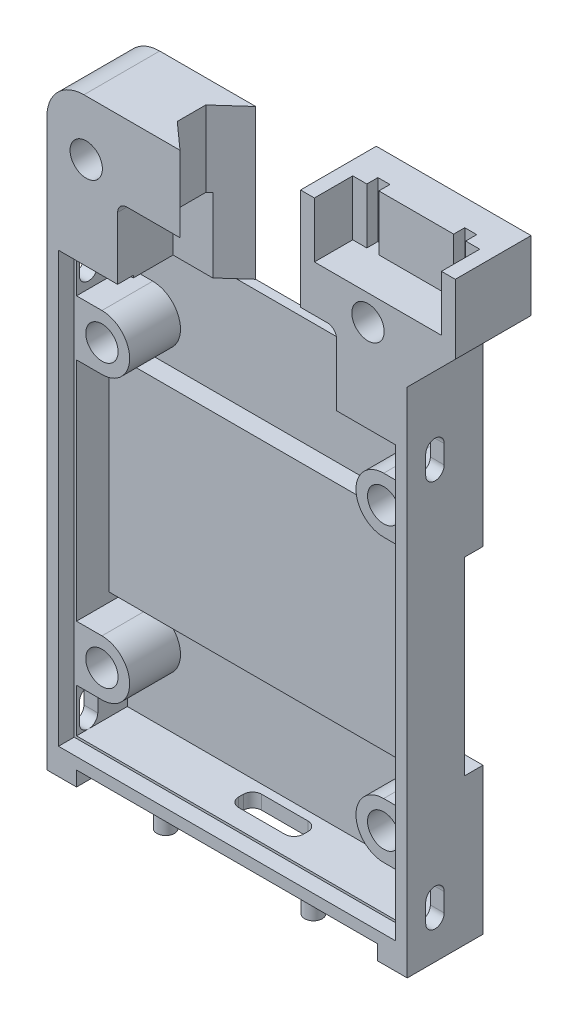
SolidWorks part; units mm, degrees
ref_plane "Front Plane" through (0, 0, 0) normal (0, 0, 1) x (1, 0, 0)
ref_plane "Top Plane" through (0, 0, 0) normal (0, 1, 0) x (1, 0, 0)
ref_plane "Right Plane" through (0, 0, 0) normal (1, 0, 0) x (0, 0, -1)
sketch "Sketch1" plane through (0, 0, 0) normal (0, 0, 1) x (1, 0, 0)
  line L0 (15.25, -20.35) -> (18, -20.35)
  line L1 (-19.5, -32.6) -> (19.5, -32.6)
  line L2 (-19.5, -32.6) -> (-19.5, 31.1)
  line L3 (-19.5, 31.1) -> (19.5, 31.1)
  line L4 (19.5, -32.6) -> (19.5, 31.1)
  line L5 (-15.25, -20.35) -> (-18, -20.35)
  line L6 (15.25, -26.35) -> (18, -26.35)
  line L7 (6.95, 31.1) -> (-15.5, 31.1) construction
  line L8 (-18, -31.1) -> (-18, 29.6)
  line L9 (-18, 29.6) -> (18, 29.6)
  line L10 (18, -31.1) -> (18, 29.6)
  line L11 (-18, -31.1) -> (18, -31.1)
  line L12 (-18, 14.9) -> (18, 14.9)
  line L13 (7.85, 14.9) -> (-4.95, 14.9) construction
  line L14 (-15.25, 4.15) -> (-18, 4.15)
  line L15 (-15.25, 10.15) -> (-18, 10.15)
  line L16 (15.25, 10.15) -> (18, 10.15)
  line L17 (15.25, 4.15) -> (18, 4.15)
  line L18 (-15.25, -26.35) -> (-18, -26.35)
  line L19 (19.5, -34.2) -> (19.5, -18.35) construction
  line L20 (-19.5, -34.2) -> (-19.5, -18.35) construction
  line L21 (15.3, -32.6) -> (-15.3, -32.6) construction
  line L22 (0, 31.1) -> (0, -32.6) construction
  line L23 (9.45, 26.9) -> (24.7, 26.9)
  line L24 (9.45, 26.9) -> (9.45, 33.9)
  line L25 (9.45, 33.9) -> (24.7, 33.9)
  line L26 (24.7, 26.9) -> (24.7, 33.9)
  line L27 (18, 29.6) -> (19.5, 31.1) construction
  line L28 (18.75, 30.35) -> (0, 30.35) construction
  line L29 (9.45, 26.9) -> (7.95, 26.9) construction
  line L30 (-7.95, 31.1) -> (7.95, 31.1)
  line L31 (-7.95, 31.1) -> (-7.95, 29.6)
  line L32 (-7.95, 29.6) -> (7.95, 29.6)
  line L33 (7.95, 31.1) -> (7.95, 29.6)
  line L34 (-7.95, 31.1) -> (7.95, 29.6) construction
  line L35 (-7.95, 29.6) -> (7.95, 31.1) construction
  line L36 (7.95, 26.9) -> (7.95, 29.6) construction
  line L37 (18, 29.6) -> (19.5, 29.6) construction
  line L38 (24.7, 26.4) -> (19.5, 21.2)
  line L39 (9.45, 33.9) -> (7.95, 33.9)
  line L40 (23.2, 33.9) -> (23.2, 26.9)
  line L41 (7.95, 33.9) -> (7.95, 31.1)
  line L42 (24.7, 30.4) -> (23.2, 30.4) construction
  line L43 (24.7, 26.9) -> (19.5, 26.9)
  line L44 (24.7, 26.9) -> (24.7, 26.4)
  line L45 (24.7, 26.4) -> (19.5, 26.4)
  line L46 (19.5, 26.9) -> (19.5, 26.4)
  circle A0 centre (15.25, -23.35) radius 1.75
  arc A1 (-15.5, 31.1) -> (-19.5, 27.1) centre (-15.5, 27.1) ccw construction
  circle A2 centre (15.25, -23.35) radius 3
  arc A3 (-15.5, 31.1) -> (-19.5, 27.1) centre (-15.5, 27.1) ccw
  arc A4 (-15.5, 29.6) -> (-18, 27.1) centre (-15.5, 27.1) ccw
  circle A6 centre (-15.25, -23.35) radius 1.75
  circle A7 centre (-15.25, -23.35) radius 1.75
  circle A8 centre (-15.25, 7.15) radius 1.75
  circle A9 centre (15.25, 7.15) radius 1.75
  circle A10 centre (15.25, 25.15) radius 1.75
  circle A11 centre (-15.25, 25.15) radius 1.75
  circle A12 centre (-15.25, -23.35) radius 3
  circle A13 centre (-15.25, -23.35) radius 3
  circle A14 centre (15.25, 7.15) radius 3
  circle A15 centre (-15.25, 7.15) radius 3
  dimension "D2" = 1.5
  dimension "D4" = 6
  dimension "D3" = 3.5
  dimension "D5" = 13.75
  dimension "D6" = 15.9
  dimension "D7" = 7
  dimension "D8" = 45
  dimension "D9" = 0.5
  dimension "D1" = 1.5
extrude "Base shape" add sketch "Sketch1" along normal up to surface (8.2 mm away) contours A15 L8 L9 L31 L3 A3 L2 L1 L4 L23 L10 A14 A2 L11 A12 | A12 L8 L18 | A12 L8 A6 | L8 A12 | A12 L5 L8 | A15 L8 L14 | A15 L8 A8 | L8 A15 | A15 L15 L8 | L23 A10 L24 L9 A4 L8 L12 L10 A11 | A4 L9 L8 | L33 L3 L31 L9 | L3 L33 L9 L24 | L24 L9 L10 L23 L4 L3 | L24 L23 L10 L9 | A14 L10 L16 | L10 A14 A9 | A14 L17 L10 | L10 A14 | L10 A2 L6 | A2 L10 A0 | L0 A2 L10 | A2 L10 | L40 L25 L24 L3 L4 L23 | L25 L40 L23 L26 | L38 L45 L4 | L45 L44 L23 L4 | L39 L41 L3 L24 region at (16.8481, -20.9099, 0) region at (17.3601, -20.8437, 0) region at (18.7469, -8.1, 0) region at (17.3601, -25.8563, 0) region at (18.1004, -23.35, 0) region at (17.3601, 4.6437, 0) region at (16.8481, 4.7099, 0) region at (18.1004, 7.15, 0) region at (17.3601, 9.6563, 0) region at (-17.3601, -25.8563, 0) region at (-0.6044, 21.831, 0) region at (-18.1004, -23.35, 0) region at (-17.9169, -23.35, 0) region at (13.725, 28.25, 0) region at (15.3803, 29.9053, 0) region at (-17.3601, -20.8437, 0) region at (22.1, 26.65, 0) region at (17.77, 31.4935, 0) region at (-17.3601, 9.6563, 0) region at (-17.4416, 29.0416, 0) region at (8.7, 30.35, 0) region at (21.2333, 24.6667, 0) region at (23.95, 30.4, 0) region at (-16.8481, 9.5901, 0) region at (-18.1004, 7.15, 0) region at (-17.3601, 4.6437, 0) region at (0, 30.35, 0) region at (8.7, 32.5, 0)
sketch "Sketch3" plane through (19.5, 0, 0) normal (1, 0, 0) x (0, 0, -1)
  line L1 (0, -18.35) -> (-2, -18.35)
  line L2 (0, -18.35) -> (0, 2.15)
  line L3 (0, 2.15) -> (-2, 2.15)
  line L4 (-2, -18.35) -> (-2, 2.15)
  line L5 (0, -18.35) -> (2, -18.35) construction
  line L6 (0, 2.15) -> (2, 2.15) construction
  line L7 (0, -32.6) -> (0, 21.2) construction
  dimension "D1" = 2
extrude "Strap cut" cut sketch "Sketch3" against normal through all
sketch "Sketch4" plane through (0, 31.1, 0) normal (0, 1, 0) x (1, 0, 0)
  line L2 (7.95, 0) -> (-5.0998, 0)
  line L4 (-15.5, 0) -> (7.95, 0) construction
  line L5 (-15.5, -8.2) -> (7.95, -8.2) construction
  line L6 (7.95, -8.2) -> (-5.0998, -8.2)
  line L12 (7.95, -8.3) -> (7.95, 0.1)
  line L13 (7.95, 0.1) -> (-4.9883, 0.1)
  line L14 (-4.9883, 0.1) -> (-7.95, -2.5553)
  line L15 (-7.95, -2.5553) -> (-7.95, -5.6447)
  line L16 (-7.95, -5.6447) -> (-4.9883, -8.3)
  line L17 (-4.9883, -8.3) -> (7.95, -8.3)
  line L18 (7.95, -8.3) -> (7.95, 0.1)
  line L19 (7.95, 0.1) -> (-4.9883, 0.1)
  line L20 (-4.9883, 0.1) -> (-7.95, -2.5553)
  line L21 (-7.95, -2.5553) -> (-7.95, -5.6447)
  line L22 (-7.95, -5.6447) -> (-4.9883, -8.3)
  line L23 (-4.9883, -8.3) -> (7.95, -8.3)
  dimension "D1" = 0.1
extrude "XT60 cut" cut sketch "Sketch4" against normal up to next contours L21 L22 L18 L20 region at (0.4142, 31.1, 4.1)
sketch "Sketch5" plane through (19.5, 0, 0) normal (1, 0, 0) x (0, 0, -1)
  line L1 (-8.2, -32.6) -> (-8.2, 21.2) construction
  line L2 (-6.2, -31.1) -> (-4.2, -31.1)
  line L3 (-6.2, -31.1) -> (-6.2, -27.1)
  line L4 (-6.2, -27.1) -> (-4.2, -27.1)
  line L5 (-4.2, -31.1) -> (-4.2, -27.1)
  line L6 (-8.2, -31.1) -> (0, -31.1) construction
  line L7 (-8.2, 14.9) -> (0, 14.9) construction
  line L8 (-6.2, 14.9) -> (-4.2, 14.9)
  line L9 (-6.2, 14.9) -> (-6.2, 10.9)
  line L10 (-6.2, 10.9) -> (-4.2, 10.9)
  line L11 (-4.2, 14.9) -> (-4.2, 10.9)
  line L14 (-5.2, -27.1) -> (-5.2, -31.1) construction
  line L15 (-5.2, 14.9) -> (-5.2, 10.9) construction
  circle A0 centre (-5.2, -28.1) radius 1
  circle A1 centre (-5.2, -30.1) radius 1
  circle A2 centre (-5.2, 13.9) radius 1
  circle A3 centre (-5.2, 11.9) radius 1
  point P20 (-5.2, -29.1)
  point P31 (-5.2, 12.9)
  dimension "D3" = 4
  dimension "D1" = 2
  dimension "D2" = 2
extrude "Power wires cut" cut sketch "Sketch5" against normal through all contours A2 | A3 | A3 A2 L9 | A3 L11 A2 | A1 | A0 | A1 L5 A0 | A1 A0 L3 region at (19.5, -30.1, 5.2) region at (19.5, -29.1, 5.9766) region at (19.5, -29.1, 4.4234) region at (19.5, -28.1, 5.2) region at (19.5, 13.9, 5.2) region at (19.5, 12.9, 5.9766) region at (19.5, 12.9, 4.4234) region at (19.5, 11.9, 5.2)
sketch "Sketch6" plane through (0, 0, 8.2) normal (0, 0, 1) x (1, 0, 0)
  line L5 (-10.85, 22.9) -> (10.85, 22.9)
  line L6 (11.85, 21.9) -> (11.85, 14.9)
  line L7 (11.85, 14.9) -> (-11.85, 14.9)
  line L12 (-11.85, 14.9) -> (-11.85, 21.9)
  line L13 (-10.85, 14.9) -> (-8.85, 14.9) construction
  arc A5 (-10.85, 22.9) -> (-11.85, 21.9) centre (-10.85, 21.9) ccw construction
  arc A6 (11.85, 21.9) -> (10.85, 22.9) centre (10.85, 21.9) ccw construction
  arc A7 (-10.85, 22.9) -> (-11.85, 21.9) centre (-10.85, 21.9) ccw
  arc A12 (11.85, 21.9) -> (10.85, 22.9) centre (10.85, 21.9) ccw
extrude "IO wires cut" cut sketch "Sketch6" against normal blind 6
sketch "Sketch7" plane through (-18, 0, 0) normal (1, 0, 0) x (0, 0, -1)
  line L6 (0, -18.35) -> (0, -20.35)
  line L7 (-2, -18.35) -> (0, -18.35)
  line L8 (-2, 2.15) -> (-2, -18.35)
  line L9 (0, 2.15) -> (-2, 2.15)
  line L12 (0, 3.15) -> (-3, 3.15)
  line L13 (-3, 3.15) -> (-3, -19.35)
  line L14 (-3, -19.35) -> (-1, -19.35)
  line L15 (-1, -19.35) -> (-1, -20.35)
  line L16 (-1, -20.35) -> (0, -20.35)
  line L17 (0, 3.15) -> (-1, 3.15)
  line L19 (0, -31.1) -> (-1, -31.1)
  line L22 (0, -31.1) -> (0, -20.35)
  line L23 (0, -20.35) -> (-1, -20.35)
  line L24 (-1, -31.1) -> (-1, -20.35)
  line L25 (0, 3.15) -> (0, 14.9)
  line L26 (0, 14.9) -> (-1, 14.9)
  line L27 (-1, 3.15) -> (-1, 14.9)
  line L28 (-5.2, 14.9) -> (0, 14.9) construction
  line L31 (0, -20.35) -> (0, -18.35) construction
  line L32 (0, 2.15) -> (-2, 2.15) construction
  line M48 (0, -20.35) -> (0, -18.35)
  line M49 (0, -18.35) -> (-2, -18.35)
  line M50 (-2, -18.35) -> (-2, 2.15)
  line M51 (-2, 2.15) -> (0, 2.15)
  line M52 (0, 2.15) -> (0, 4.15)
  line M53 (0, 4.15) -> (-8.2, 4.15)
  line M55 (-8.2, -20.35) -> (0, -20.35)
  dimension "D1" = 1
extrude "Bottom" add sketch "Sketch7" along normal up to surface (36 mm away) contours L27 L25 L26 M53 | L27 L12 M52 M53 | L14 L15 L12 L13 M55 M48 M49 M50 M51 M52 | L24 L19 L22 M55 region at (-18, -8.5273, 2.2091) region at (-18, -25.725, 0.5) region at (-18, 3.65, 0.5) region at (-18, 9.525, 0.5) up to face at (18, -8.1, 2.55)
sketch "Sketch9" plane through (0, 0, 0) normal (0, 0, -1) x (-1, 0, 0)
  circle A0 centre (15.25, -23.35) radius 1.75 construction
  circle A1 centre (-15.25, 7.15) radius 1.75 construction
  circle A2 centre (15.25, 7.15) radius 1.75 construction
  circle A3 centre (15.25, -23.35) radius 1.75 construction
  circle A4 centre (15.25, -23.35) radius 1.75
  circle A5 centre (-15.25, 7.15) radius 1.75
  circle A6 centre (15.25, 7.15) radius 1.75
  circle A7 centre (15.25, -23.35) radius 1.75
  circle A8 centre (-15.25, -23.35) radius 1.75 construction
  circle A9 centre (-15.25, -23.35) radius 1.75
extrude "Bottom holes" cut sketch "Sketch9" against normal up to next contours A5 | A6 | A4 | A9 region at (-15.25, -23.35, 0) region at (15.25, 7.15, 0) region at (-15.25, 7.15, 0) region at (15.25, -23.35, 0)
sketch "Sketch8" plane through (0, 0, 8.2) normal (0, 0, 1) x (1, 0, 0)
  line L0 (-6.2152, 14.9) -> (-18, 14.9) construction
  line L1 (-18.25, 15.15) -> (18.25, 15.15)
  line L2 (-18.25, 15.15) -> (-18.25, -31.35)
  line L3 (-18.25, -31.35) -> (18.25, -31.35)
  line L4 (18.25, 15.15) -> (18.25, -31.35)
  line L5 (-18, 14.9) -> (-18.25, 14.9) construction
  line L6 (-18, 14.9) -> (-18, 15.15) construction
  line L7 (18, 14.9) -> (18.25, 14.9) construction
  line L8 (-18, -31.1) -> (-18, -31.35) construction
  dimension "D1" = 0.25
extrude "PCB cut" cut sketch "Sketch8" against normal blind 1.7
sketch "Sketch11" plane through (0, -32.6, 0) normal (0, -1, 0) x (1, 0, 0)
  line L0 (19.5, 8.2) -> (19.5, 0) construction
  line L1 (-19.5, 8.2) -> (19.5, 8.2)
  line L2 (-19.5, 8.2) -> (-19.5, -1.8)
  line L3 (-19.5, -1.8) -> (19.5, -1.8)
  line L4 (19.5, 8.2) -> (19.5, -1.8)
  line L5 (-19.5, 3.2) -> (19.5, 3.2) construction
  line L6 (0, -1.8) -> (0, 8.2) construction
  line L8 (-2.5, 4.45) -> (2.5, 4.45)
  line L9 (-3.5, 3.45) -> (-3.5, 2.95)
  line L10 (-2.5, 1.95) -> (2.5, 1.95)
  line L11 (3.5, 3.45) -> (3.5, 2.95)
  line L12 (-3.5, 4.45) -> (3.5, 1.95) construction
  line L13 (-3.5, 1.95) -> (3.5, 4.45) construction
  arc A0 (2.5, 4.45) -> (3.5, 3.45) centre (2.5, 3.45) cw
  arc A1 (2.5, 1.95) -> (3.5, 2.95) centre (2.5, 2.95) ccw
  arc A2 (-3.5, 2.95) -> (-2.5, 1.95) centre (-2.5, 2.95) ccw
  arc A3 (-2.5, 4.45) -> (-3.5, 3.45) centre (-2.5, 3.45) ccw
  point P11 (0, 3.2)
  dimension "D4" = 1
  dimension "D1" = 10
  dimension "D2" = 7
  dimension "D3" = 2.5
extrude "Ledbar wires cut" cut sketch "Sketch11" against normal up to next contours L8 A3 L9 A2 L10 A1 L11 A0 region at (0, -32.6, 3.2)
sketch "Sketch13" plane through (0, -32.6, 0) normal (0, -1, 0) x (1, 0, 0)
  line L0 (-19.5, 8.2) -> (19.5, 8.2) construction
  line L1 (19.5, 0) -> (16.3, 0)
  line L2 (19.5, 0) -> (19.5, 8.2)
  line L3 (19.5, 8.2) -> (16.3, 8.2)
  line L4 (16.3, 0) -> (16.3, 8.2)
  line L5 (16.1, -1.8) -> (16.1, 8.2) construction
  line L6 (0, 8.2) -> (0, 0) construction
  line L7 (-19.5, 0) -> (-16.3, 0)
  line L8 (-19.5, 0) -> (-19.5, 8.2)
  line L9 (-19.5, 8.2) -> (-16.3, 8.2)
  line L10 (-16.3, 0) -> (-16.3, 8.2)
  dimension "D1" = 0.2
extrude "Ledbar sides" add sketch "Sketch13" along normal blind 1.6
sketch "Sketch14" plane through (0, -32.6, 0) normal (0, -1, 0) x (1, 0, 0)
  circle A0 centre (8, 6.85) radius 0.95
  circle A1 centre (-8, 6.85) radius 0.95
  dimension "D1" = 1.9
extrude "Ledbar mounts" add sketch "Sketch14" along normal blind 2
sketch "Sketch16" plane through (0, 33.9, 0) normal (0, 1, 0) x (1, 0, 0)
  line L0 (7.95, -6.125) -> (24.7, -6.125) construction
  line L1 (7.95, -8.2) -> (24.7, -8.2) construction
  line L2 (21.675, -2.85) -> (20.375, -2.85)
  line L3 (20.375, -4.05) -> (20.375, -2.85)
  line L4 (9.45, -4.05) -> (23.2, -4.05)
  line L5 (9.45, -4.05) -> (9.45, -8.2)
  line L6 (9.45, -8.2) -> (23.2, -8.2)
  line L7 (23.2, -4.05) -> (23.2, -8.2)
  line L8 (9.45, -4.05) -> (23.2, -8.2) construction
  line L9 (9.45, -8.2) -> (23.2, -4.05) construction
  line L10 (24.7, -8.2) -> (24.7, 0) construction
  line L11 (7.95, -8.2) -> (7.95, 0) construction
  line L12 (16.325, -8.2) -> (16.325, -4.05) construction
  line L13 (11.625, -2.85) -> (11.625, -4.05) construction
  line L14 (10.975, -4.05) -> (12.275, -4.05)
  line L15 (10.975, -4.05) -> (10.975, -2.85)
  line L16 (10.975, -2.85) -> (12.275, -2.85)
  line L17 (12.275, -4.05) -> (12.275, -2.85)
  line L18 (10.975, -2.85) -> (10.975, -8.2) construction
  line L19 (21.675, -4.05) -> (21.675, -2.85)
  point P6 (16.325, -6.125)
  dimension "D1" = 13.75
  dimension "D2" = 4.15
  dimension "D3" = 1.3
  dimension "D4" = 1.2
  dimension "D5" = 4.7
extrude "Balance plug cut" cut sketch "Sketch16" against normal blind 6 contours L7 L4 L5 L6 | L4 L17 L16 L15 | L4 L19 L2 L3 region at (21.025, 33.9, 3.45) region at (16.325, 33.9, 6.125) region at (11.625, 33.9, 3.45)
sketch "Sketch10" [suppressed] plane through (0, 0, 2) normal (0, 0, -1) x (-1, 0, 0)
  line L0 (0, 2.15) -> (0, -18.35) construction
  line L1 (19.5, 2.15) -> (-19.5, 2.15) construction
  line L2 (19.5, -18.35) -> (-19.5, -18.35) construction
  line L3 (19.5, 2.15) -> (19.5, -18.35) construction
  line L4 (-19.5, 1.15) -> (19.5, 1.15)
  line L5 (-19.5, 1.15) -> (-19.5, 0.65)
  line L6 (-19.5, 0.65) -> (19.5, 0.65)
  line L7 (19.5, 1.15) -> (19.5, 0.65)
  line L8 (-19.5, 1.15) -> (19.5, 0.65) construction
  line L9 (-19.5, 0.65) -> (19.5, 1.15) construction
  line L10 (-19.5, 2.15) -> (19.5, 2.15) construction
  line L11 (-19.5, -1.35) -> (19.5, -1.35)
  line L12 (19.5, -0.85) -> (19.5, -1.35)
  line L13 (-19.5, -0.85) -> (19.5, -0.85)
  line L14 (-19.5, -0.85) -> (-19.5, -1.35)
  line L15 (-19.5, -3.35) -> (19.5, -3.35)
  line L16 (19.5, -2.85) -> (19.5, -3.35)
  line L17 (-19.5, -2.85) -> (19.5, -2.85)
  line L18 (-19.5, -2.85) -> (-19.5, -3.35)
  line L19 (-19.5, -5.35) -> (19.5, -5.35)
  line L20 (19.5, -4.85) -> (19.5, -5.35)
  line L21 (-19.5, -4.85) -> (19.5, -4.85)
  line L22 (-19.5, -4.85) -> (-19.5, -5.35)
  line L23 (-19.5, -7.35) -> (19.5, -7.35)
  line L24 (19.5, -6.85) -> (19.5, -7.35)
  line L25 (-19.5, -6.85) -> (19.5, -6.85)
  line L26 (-19.5, -6.85) -> (-19.5, -7.35)
  line L27 (-19.5, -9.35) -> (19.5, -9.35)
  line L28 (19.5, -8.85) -> (19.5, -9.35)
  line L29 (-19.5, -8.85) -> (19.5, -8.85)
  line L30 (-19.5, -8.85) -> (-19.5, -9.35)
  line L31 (-19.5, -11.35) -> (19.5, -11.35)
  line L32 (19.5, -10.85) -> (19.5, -11.35)
  line L33 (-19.5, -10.85) -> (19.5, -10.85)
  line L34 (-19.5, -10.85) -> (-19.5, -11.35)
  line L35 (-19.5, -13.35) -> (19.5, -13.35)
  line L36 (19.5, -12.85) -> (19.5, -13.35)
  line L37 (-19.5, -12.85) -> (19.5, -12.85)
  line L38 (-19.5, -12.85) -> (-19.5, -13.35)
  line L39 (-19.5, -15.35) -> (19.5, -15.35)
  line L40 (19.5, -14.85) -> (19.5, -15.35)
  line L41 (-19.5, -14.85) -> (19.5, -14.85)
  line L42 (-19.5, -14.85) -> (-19.5, -15.35)
  line L43 (-19.5, -17.35) -> (19.5, -17.35)
  line L44 (19.5, -16.85) -> (19.5, -17.35)
  line L45 (-19.5, -16.85) -> (19.5, -16.85)
  line L46 (-19.5, -16.85) -> (-19.5, -17.35)
  point P6 (0, 0.9)
  dimension "D1" = 1
  dimension "D2" = 0.5
  dimension "D4" = 2
  dimension "D3" = 10
extrude "3D print ribs" [suppressed] add sketch "Sketch10" along normal up to surface (2 mm away) up to face at (-17, 7.15, 0)
sketch "Sketch15" [suppressed] plane through (0, 0, 0) normal (0, 0, -1) x (-1, 0, 0)
  line L0 (-8, -34.6) -> (-8, -32.6) construction
  line L1 (-8.95, -34.6) -> (-7.05, -34.6) construction
  line L2 (-8.95, -32.6) -> (-7.05, -32.6) construction
  line L3 (0, -32.6) -> (0, 14.9) construction
  line L4 (-8.25, -34.6) -> (-7.75, -34.6)
  line L5 (-8.25, -34.6) -> (-8.25, -32.6)
  line L6 (-8.25, -32.6) -> (-7.75, -32.6)
  line L7 (-7.75, -34.6) -> (-7.75, -32.6)
  line L8 (-8.25, -34.6) -> (-7.75, -32.6) construction
  line L9 (-8.25, -32.6) -> (-7.75, -34.6) construction
  line L10 (16.3, -32.6) -> (-16.3, -32.6) construction
  line L11 (-7.95, 14.9) -> (5.0998, 14.9) construction
  line L12 (8.25, -32.6) -> (7.75, -32.6)
  line L13 (7.75, -34.6) -> (7.75, -32.6)
  line L14 (8.25, -34.6) -> (7.75, -34.6)
  line L15 (8.25, -34.6) -> (8.25, -32.6)
  point P6 (-8, -33.6)
  dimension "D1" = 0.5
extrude "3D print led supports" [suppressed] add sketch "Sketch15" against normal up to next
